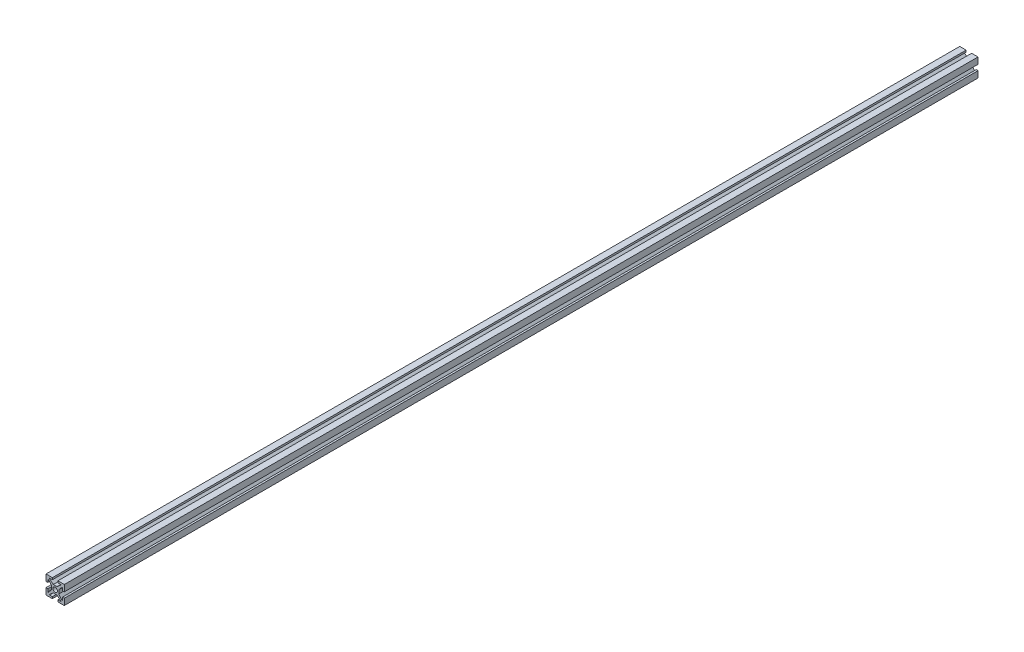
SolidWorks part; units mm, degrees
ref_plane "Front Plane" through (0, 0, 0) normal (0, 0, 1) x (1, 0, 0)
ref_plane "Top Plane" through (0, 0, 0) normal (0, 1, 0) x (1, 0, 0)
ref_plane "Right Plane" through (0, 0, 0) normal (1, 0, 0) x (0, 0, -1)
sketch "Esquisse1" plane through (0, 0, 0) normal (0, 0, 1) x (1, 0, 0)
  line L0 (0, 2) -> (0, 1.25)
  line L1 (-3.0678, 3.7351) -> (-1, 2)
  line L2 (-2.9714, 4) -> (-1.5, 4)
  line L3 (-1.5, 4) -> (-1.5, 5)
  line L4 (-5, 5) -> (-5, 1.5)
  line L5 (-5, 1.5) -> (-4, 1.5)
  line L6 (-4, 1.5) -> (-4, 2.9714)
  line L7 (-5, 5) -> (-1.5, 5)
  line L8 (-3.7351, 3.0678) -> (-2, 1)
  line L9 (-2, 1) -> (-2, 0)
  line L10 (-2, 0) -> (-1.25, 0)
  line L11 (-1, 2) -> (0, 2)
  arc A0 (-2.9714, 4) -> (-3.0678, 3.7351) centre (-2.9714, 3.85) ccw
  arc A1 (-4, 2.9714) -> (-3.7351, 3.0678) centre (-3.85, 2.9714) cw
  arc A2 (0, 1.25) -> (-1.25, 0) centre (0, 0) ccw
  dimension "D7" = 0.15
  dimension "D4" = 1.25
  dimension "D1" = 3.5
  dimension "D2" = 1
  dimension "D3" = 1
  dimension "D5" = 5
  dimension "D6" = 2
  dimension "D8" = 5
  dimension "D9" = 40
ref_axis "Axe1" through (0, -0.1269, 0) along (0, 1, 0)
extrude "Boss.-Extru.1" add sketch "Esquisse1" along normal blind 500
ref_axis "Axe2" through (0, 0, 105) along (0, 0, -1)
pattern_circular "Répétition circulaire1" count 4 every 90 about axis through (0, 0, 105) along (0, 0, -1) of "Boss.-Extru.1"
